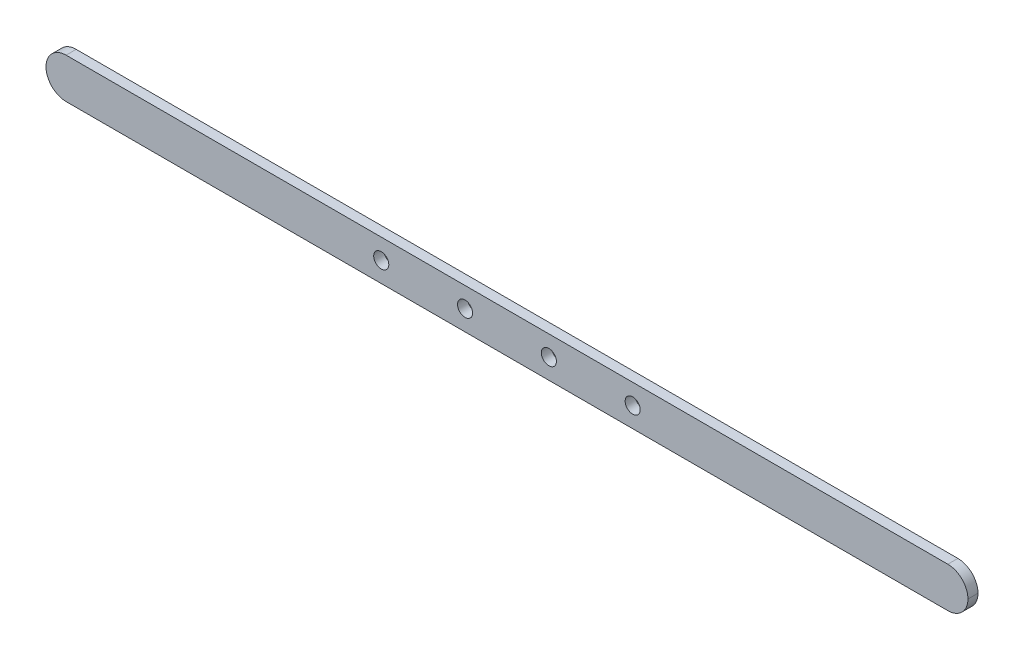
SolidWorks part; units mm, degrees
ref_plane "Front Plane" through (0, 0, 0) normal (0, 0, 1) x (1, 0, 0)
ref_plane "Top Plane" through (0, 0, 0) normal (0, 1, 0) x (1, 0, 0)
ref_plane "Right Plane" through (0, 0, 0) normal (1, 0, 0) x (0, 0, -1)
sketch "Sketch1" plane through (0, 0, 0) normal (0, 0, 1) x (1, 0, 0)
  line L0 (0, 0) -> (75, 0)
  line L1 (-275, -12) -> (275, -12)
  line L2 (-275, -12) -> (-275, 12)
  line L3 (-275, 12) -> (275, 12)
  line L4 (275, -12) -> (275, 12)
  line L5 (-275, -12) -> (275, 12) construction
  line L6 (-275, 12) -> (275, -12) construction
  circle A0 centre (75, 0) radius 4.5
  circle A1 centre (25, 0) radius 4.5
  circle A2 centre (-25, 0) radius 4.5
  circle A3 centre (-75, 0) radius 4.5
  point P0 (0, 0)
  dimension "D4" = 9
  dimension "D1" = 24
  dimension "D2" = 550
  dimension "D3" = 75
  dimension "D6" = 25
  dimension "D5" = 4
extrude "Boss-Extrude1" add sketch "Sketch1" along normal blind 6 contours L1 L4 L3 L2 A3 A2 A1 A0 region at (-269.4948, 0, 0)
fillet "Fillet2" radius 12 4 edges at (-275, -12, 3) (-275, 12, 3) (275, 12, 3) (275, -12, 3)
